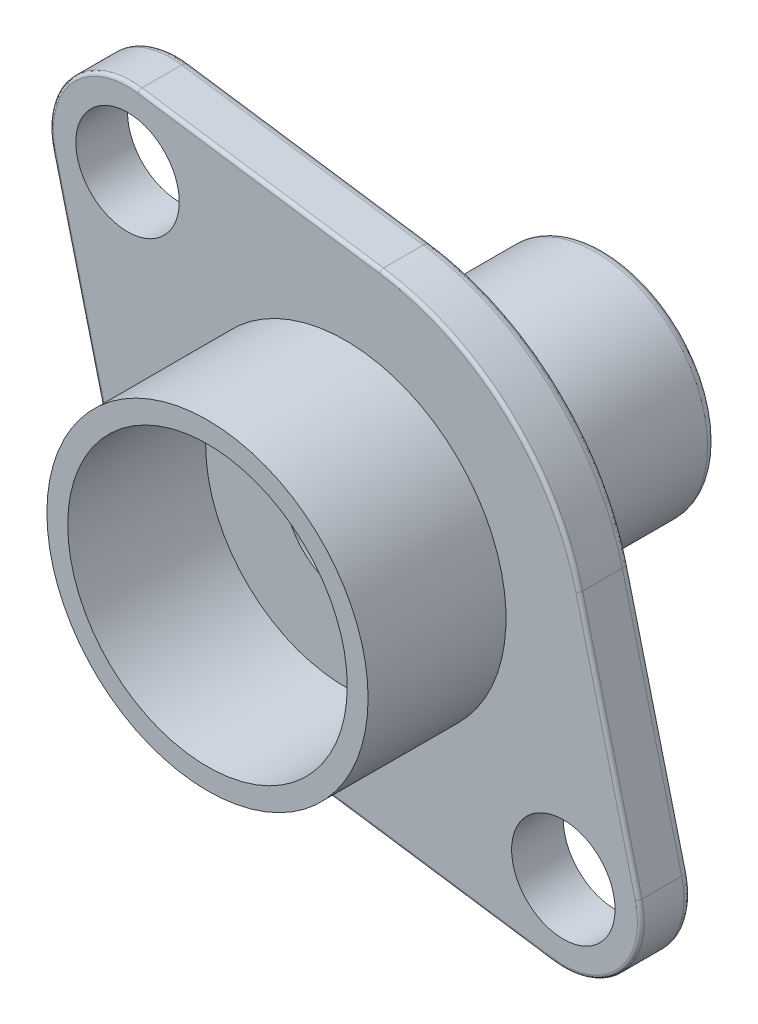
SolidWorks part; units mm, degrees
ref_plane "Front Plane" through (0, 0, 0) normal (0, 0, 1) x (1, 0, 0)
ref_plane "Top Plane" through (0, 0, 0) normal (0, 1, 0) x (1, 0, 0)
ref_plane "Right Plane" through (0, 0, 0) normal (1, 0, 0) x (0, 0, -1)
sketch "Sketch1" plane through (0, 0, 0) normal (0, 0, 1) x (1, 0, 0)
  line L0 (-2.0091, -13.8538) -> (11.9955, -15.8952)
  line L1 (17.0011, -10.3491) -> (13.5587, 3.4009)
  line L2 (2.0091, 13.8538) -> (-11.9955, 15.8952)
  line L3 (-17.0011, 10.3491) -> (-13.5587, -3.4009)
  spline S1 degree 3 poles (-13.5587, -3.4009) (-13.2215, -4.7478) (-12.6969, -6.0124) (-11.8111, -7.4921) (-11.6213, -7.784) (-11.2235, -8.3489) (-11.0152, -8.6225) (-10.3626, -9.4177) (-9.8908, -9.9136) (-8.8735, -10.8364) (-8.3232, -11.266) (-7.1782, -12.0304) (-6.5822, -12.3675) (-5.6533, -12.8066) (-5.3379, -12.9418) (-4.6951, -13.1895) (-4.3668, -13.3023) (-3.3714, -13.6032) (-2.6961, -13.7537) (-2.0091, -13.8538) knots 0 0 0 0 0.25 0.25 0.3125 0.3125 0.375 0.375 0.5 0.5 0.625 0.625 0.75 0.75 0.8125 0.8125 0.875 0.875 1 1 1 1
  spline S2 degree 3 poles (11.9955, -15.8952) (12.3624, -15.9487) (12.7294, -15.9565) (13.2803, -15.9005) (13.4636, -15.8703) (13.821, -15.7887) (13.9964, -15.7371) (14.5124, -15.5507) (14.8464, -15.3812) (15.3017, -15.0747) (15.4468, -14.9636) (15.7236, -14.7235) (15.8561, -14.5936) (16.2267, -14.1821) (16.4362, -13.8826) (16.695, -13.396) (16.7722, -13.2264) (16.9038, -12.883) (17.0135, -12.5339) (17.0803, -12.1737) (17.1251, -11.8076) (17.1362, -11.6221) (17.1356, -11.072) (17.0912, -10.7087) (17.0011, -10.3491) knots 0 0 0 0 0.125 0.125 0.1875 0.1875 0.25 0.25 0.375 0.375 0.4375 0.4375 0.5 0.5 0.625 0.625 0.6875 0.6875 0.75 0.8125 0.8125 0.875 0.875 1 1 1 1
  spline S3 degree 3 poles (13.5587, 3.4009) (13.2215, 4.7478) (12.6969, 6.0124) (11.8111, 7.4921) (11.6213, 7.784) (11.2235, 8.3489) (11.0152, 8.6225) (10.3626, 9.4177) (9.8908, 9.9136) (8.8735, 10.8364) (8.3232, 11.266) (7.1782, 12.0304) (6.5822, 12.3675) (5.6533, 12.8066) (5.3379, 12.9418) (4.6951, 13.1895) (4.3668, 13.3023) (3.3714, 13.6032) (2.6961, 13.7537) (2.0091, 13.8538) knots 0 0 0 0 0.25 0.25 0.3125 0.3125 0.375 0.375 0.5 0.5 0.625 0.625 0.75 0.75 0.8125 0.8125 0.875 0.875 1 1 1 1
  spline S4 degree 3 poles (-11.9955, 15.8952) (-12.3624, 15.9487) (-12.7294, 15.9565) (-13.2803, 15.9005) (-13.4636, 15.8703) (-13.821, 15.7887) (-13.9964, 15.7371) (-14.5124, 15.5507) (-14.8464, 15.3812) (-15.3017, 15.0747) (-15.4468, 14.9636) (-15.7236, 14.7235) (-15.8561, 14.5936) (-16.2267, 14.1821) (-16.4362, 13.8826) (-16.695, 13.396) (-16.7722, 13.2264) (-16.9038, 12.883) (-17.0135, 12.5339) (-17.0803, 12.1737) (-17.1251, 11.8076) (-17.1362, 11.6221) (-17.1356, 11.072) (-17.0912, 10.7087) (-17.0011, 10.3491) knots 0 0 0 0 0.125 0.125 0.1875 0.1875 0.25 0.25 0.375 0.375 0.4375 0.4375 0.5 0.5 0.625 0.625 0.6875 0.6875 0.75 0.8125 0.8125 0.875 0.875 1 1 1 1
extrude "Extrude1" add sketch "Sketch1" along normal blind 3
sketch "Sketch3" plane through (0, 0, 0) normal (0, 0, -1) x (-1, 0, 0)
  line L8 (11.6186, -2.9152) -> (15.061, 10.8348)
  line L9 (12.284, 13.9161) -> (-1.7206, 11.8747)
  line L10 (-11.6186, 2.9152) -> (-15.061, -10.8348)
  line L11 (-12.284, -13.9161) -> (1.7206, -11.8747)
  line L12 (11.6186, -2.9152) -> (13.3659, 4.0639)
  line L13 (5.3752, 12.909) -> (-1.7206, 11.8747)
  line L14 (-11.6186, 2.9152) -> (-13.3659, -4.0639)
  line L15 (-5.3752, -12.909) -> (1.7206, -11.8747)
  arc A0 (-11.3931, -7.6423) -> (-13.3659, -4.0639) centre (-10.4557, -4.7925) cw
  arc A1 (-8.7383, -10.5832) -> (-5.3752, -12.909) centre (-5.8079, -9.9404) ccw
  arc A2 (11.3931, 7.6423) -> (13.3659, 4.0639) centre (10.4557, 4.7925) cw
  arc A3 (5.3752, 12.909) -> (8.7383, 10.5832) centre (5.8079, 9.9404) cw
  spline S5 degree 3 poles (-8.7383, -10.5832) (-8.7595, -10.4864) (-8.7843, -10.3903) (-8.8879, -10.0439) (-8.9866, -9.8029) (-9.2305, -9.3412) (-9.3774, -9.1191) (-9.7068, -8.7141) (-9.89, -8.529) (-10.2942, -8.194) (-10.5136, -8.0461) (-10.9498, -7.8104) (-11.1671, -7.7166) (-11.3931, -7.6423) knots 0.800704 0.800704 0.800704 0.800704 0.8125 0.8125 0.84375 0.84375 0.875 0.875 0.90625 0.90625 0.9375 0.9375 0.965743 0.965743 0.965743 0.965743
  spline S7 degree 3 poles (8.7383, 10.5832) (8.7595, 10.4864) (8.7843, 10.3903) (8.8879, 10.0439) (8.9866, 9.8029) (9.2305, 9.3412) (9.3774, 9.1191) (9.7068, 8.7141) (9.89, 8.529) (10.2942, 8.194) (10.5136, 8.0461) (10.9498, 7.8104) (11.1671, 7.7166) (11.3931, 7.6423) knots 0.800704 0.800704 0.800704 0.800704 0.8125 0.8125 0.84375 0.84375 0.875 0.875 0.90625 0.90625 0.9375 0.9375 0.965743 0.965743 0.965743 0.965743
  spline S8 degree 3 poles (-1130.4626, 2763.144) (-348.6267, 594.5225) (-63.204, -43.0117) (5.3589, -10.7341) (5.624, -10.5971) (6.1395, -10.3059) (6.3905, -10.1514) (7.124, -9.6623) (7.5868, -9.3019) (8.4602, -8.5124) (8.8733, -8.0793) (9.6221, -7.1679) (9.9602, -6.6882) (10.565, -5.6816) (10.8332, -5.1527) (48.3824, 85.3079) (-1051.0871, 564.2801) (2917.9696, -691.422) knots -15.707481 -15.707481 -15.707481 -15.707481 0.25 0.25 0.3125 0.3125 0.375 0.375 0.5 0.5 0.625 0.625 0.75 0.75 0.875 0.875 21.359933 21.359933 21.359933 21.359933 only from (1.7206, -11.8747) to (11.6186, -2.9152)
  spline S9 degree 3 poles (-984.5878, 37.3205) (-154.4074, -9.4557) (15.1111, -5.5139) (15.1363, 11.6432) (15.1112, 11.8493) (15.0136, 12.2432) (14.9399, 12.4363) (14.7485, 12.797) (14.6324, 12.9634) (14.3587, 13.2679) (14.2036, 13.4027) (13.8669, 13.6299) (13.6815, 13.7242) (13.2994, 13.8626) (13.0998, 13.9084) (-7.7841, 16.0407) (-26.1901, -240.0181) (-40.2926, -984.6948) knots -10.288294 -10.288294 -10.288294 -10.288294 0.125 0.125 0.25 0.25 0.375 0.375 0.5 0.5 0.625 0.625 0.75 0.75 0.875 0.875 13.538225 13.538225 13.538225 13.538225 only from (15.061, 10.8348) to (12.284, 13.9161)
  spline S10 degree 3 poles (1130.4626, -2763.144) (348.6267, -594.5225) (63.204, 43.0117) (-5.3589, 10.7341) (-5.624, 10.5971) (-6.1395, 10.3059) (-6.3905, 10.1514) (-7.124, 9.6623) (-7.5868, 9.3019) (-8.4602, 8.5124) (-8.8733, 8.0793) (-9.6221, 7.1679) (-9.9602, 6.6882) (-10.565, 5.6816) (-10.8332, 5.1527) (-48.3824, -85.3079) (1051.0871, -564.2801) (-2917.9696, 691.422) knots -15.707481 -15.707481 -15.707481 -15.707481 0.25 0.25 0.3125 0.3125 0.375 0.375 0.5 0.5 0.625 0.625 0.75 0.75 0.875 0.875 21.359933 21.359933 21.359933 21.359933 only from (-1.7206, 11.8747) to (-11.6186, 2.9152)
  spline S11 degree 3 poles (984.5869, -37.3202) (154.4068, 9.4557) (-15.1111, 5.5139) (-15.1363, -11.6432) (-15.1112, -11.8493) (-15.0136, -12.2432) (-14.9399, -12.4363) (-14.7485, -12.797) (-14.6324, -12.9634) (-14.3587, -13.2679) (-14.2036, -13.4027) (-13.8669, -13.6299) (-13.6815, -13.7242) (-13.2994, -13.8626) (-13.0998, -13.9084) (7.7842, -16.0408) (26.1902, 240.0222) (40.2924, 984.699) knots -10.288276 -10.288276 -10.288276 -10.288276 0.125 0.125 0.25 0.25 0.375 0.375 0.5 0.5 0.625 0.625 0.75 0.75 0.875 0.875 13.538322 13.538322 13.538322 13.538322 only from (-15.061, -10.8348) to (-12.284, -13.9161)
  spline S12 degree 3 poles (1.7206, -11.8747) (2.8982, -11.7031) (4.0214, -11.3637) (5.3589, -10.7341) (5.624, -10.5971) (6.1395, -10.3059) (6.3905, -10.1514) (7.124, -9.6623) (7.5868, -9.3019) (8.4602, -8.5124) (8.8733, -8.0793) (9.6221, -7.1679) (9.9602, -6.6882) (10.565, -5.6816) (10.8332, -5.1527) (11.2887, -4.0554) (11.4741, -3.4923) (11.6186, -2.9152) knots 0 0 0 0 0.25 0.25 0.3125 0.3125 0.375 0.375 0.5 0.5 0.625 0.625 0.75 0.75 0.875 0.875 1 1 1 1
  spline S14 degree 3 poles (-1.7206, 11.8747) (-2.8982, 11.7031) (-4.0214, 11.3637) (-5.3589, 10.7341) (-5.624, 10.5971) (-6.1395, 10.3059) (-6.3905, 10.1514) (-7.124, 9.6623) (-7.5868, 9.3019) (-8.4602, 8.5124) (-8.8733, 8.0793) (-9.6221, 7.1679) (-9.9602, 6.6882) (-10.565, 5.6816) (-10.8332, 5.1527) (-11.2887, 4.0554) (-11.4741, 3.4923) (-11.6186, 2.9152) knots 0 0 0 0 0.25 0.25 0.3125 0.3125 0.375 0.375 0.5 0.5 0.625 0.625 0.75 0.75 0.875 0.875 1 1 1 1
  dimension "D4" = 3
  dimension "D1" = 2
extrude "Extrude3" cut sketch "Sketch3" against normal blind 1
sketch "Sketch2" plane through (0, 0, 0) normal (0, 0, -1) x (-1, 0, 0)
  circle A0 centre (0, 0) radius 6.5
extrude "Extrude2" add sketch "Sketch2" along normal blind 12 and the other way blind 2
fillet "Fillet1" radius 3 1 edges at (6.5, 0, 1)
fillet "Fillet2" radius 0.5 33 edges at (-6.5, 0, -12)
fillet "Fillet3" radius 0.2 8 edges
sketch "Sketch4" plane through (0, 0, 3) normal (0, 0, 1) x (1, 0, 0)
  circle A0 centre (0, 0) radius 8.1056
  circle A1 centre (0, 0) radius 9.3135
extrude "Extrude4" add sketch "Sketch4" along normal blind 8
sketch "Sketch5" plane through (0, 0, -12) normal (0, 0, -1) x (-1, 0, 0)
  circle A0 centre (0, 0) radius 3.5
extrude "Extrude5" cut sketch "Sketch5" against normal through all
sketch "Sketch7" plane through (0, 0, 3) normal (0, 0, 1) x (1, 0, 0)
  circle A0 centre (-12.6379, 11.4465) radius 3
  circle A1 centre (12.6379, -11.4465) radius 3
extrude "Extrude6" cut sketch "Sketch7" against normal blind 17
